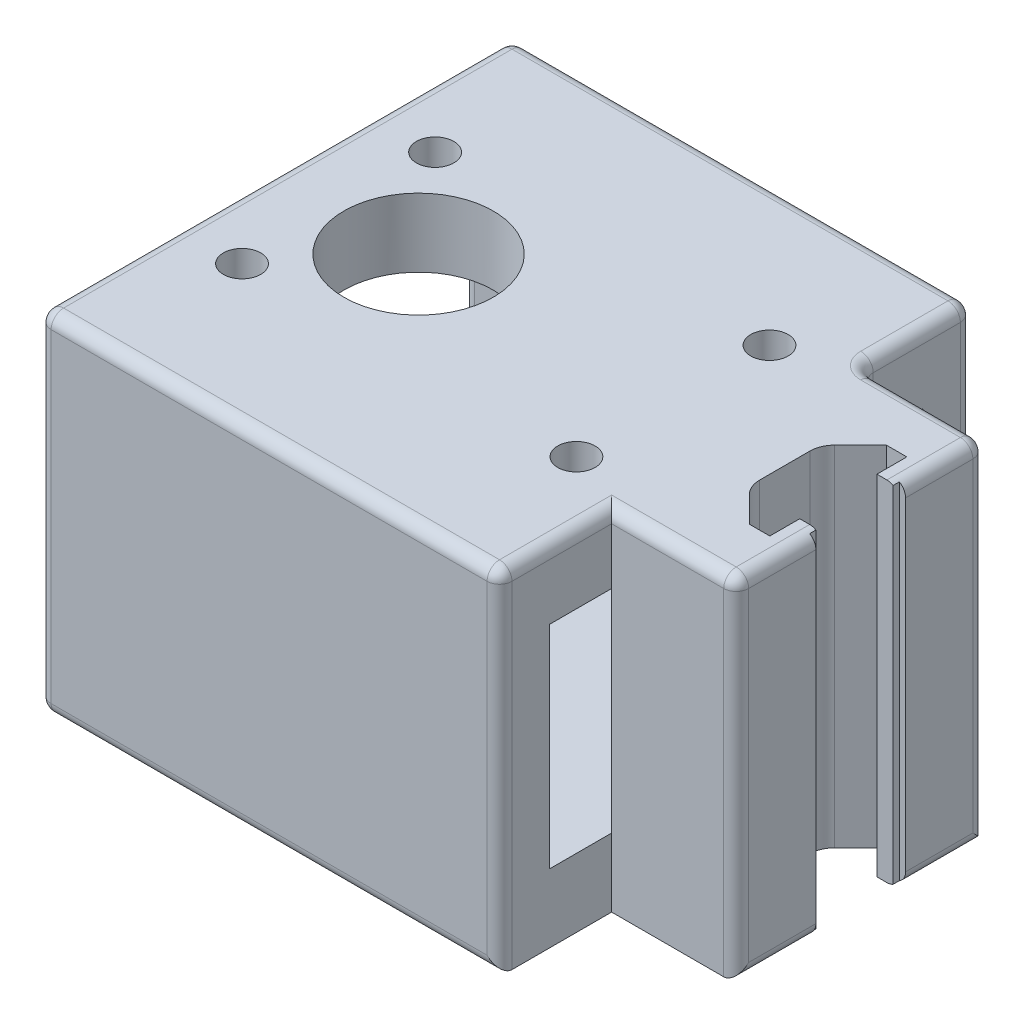
SolidWorks part; units mm, degrees
ref_plane "Front Plane" through (0, 0, 0) normal (0, 0, 1) x (1, 0, 0)
ref_plane "Top Plane" through (0, 0, 0) normal (0, 1, 0) x (1, 0, 0)
ref_plane "Right Plane" through (0, 0, 0) normal (1, 0, 0) x (0, 0, -1)
sketch "Sketch2" plane through (0, 0, 0) normal (1, 0, 0) x (0, 0, -1)
  line L0 (0, -8.5) -> (0, -24.413) construction
  line L1 (19, -14) -> (4, -14)
  line L2 (19, -14) -> (19, 14)
  line L3 (19, 14) -> (-19, 14)
  line L4 (-19, -14) -> (-19, 14)
  line L5 (19, -14) -> (-19, 14) construction
  line L6 (19, 14) -> (-19, -14) construction
  line L7 (-15, -8.5) -> (15, -8.5)
  line L8 (-15, -8.5) -> (-15, 8.5)
  line L9 (-15, 8.5) -> (15, 8.5)
  line L10 (15, -8.5) -> (15, 8.5)
  line L11 (-15, -8.5) -> (15, 8.5) construction
  line L12 (-15, 8.5) -> (15, -8.5) construction
  line L13 (0, -18) -> (-4, -14)
  line L14 (0, -18) -> (4, -14)
  line L15 (-4, -14) -> (-19, -14)
  point P0 (0, 0)
  point P5 (0, 0)
  dimension "D1" = 28
  dimension "D2" = 38
  dimension "D3" = 17
  dimension "D4" = 30
  dimension "D5" = 5.6569
  dimension "D6" = 45
extrude "Boss-Extrude1" add sketch "Sketch2" along normal blind 37
sketch "Sketch3" plane through (0, 14, 0) normal (0, 1, 0) x (1, 0, 0)
  line L0 (37, 19) -> (0, 19) construction
  line L1 (0, 0) -> (37, 0) construction
  line L2 (0, 19) -> (0, -19) construction
  line L3 (37, -19) -> (0, -19) construction
  line L4 (18.5, 19) -> (18.5, -19) construction
  line L5 (37, 19) -> (37, -19) construction
  circle A12 centre (11.5, 0) radius 6
  point P16 (18.5, 0)
  dimension "D1" = 7
  dimension "D5" = 12
extrude "Cut-Extrude1" cut sketch "Sketch3" against normal up to surface (5.5 mm away) contours A12 region at (11.5, 14, 0) up to face at (18.5, 8.5, 0)
sketch "Sketch4" plane through (0, 14, 0) normal (0, 1, 0) x (1, 0, 0)
  line L0 (0, 0) -> (37, 0) construction
  line L1 (37, 19) -> (37, -19) construction
  line L2 (18.5, 0) -> (1.119, 10.0349) construction
  line L3 (18.5, 0) -> (5.0766, 7.75) construction
  circle A0 centre (18.5, 0) radius 15.5 construction
  circle A1 centre (5.0766, 7.75) radius 1.5
  circle A2 centre (18.5, 15.5) radius 1.5 [skipped]
  circle A3 centre (31.9234, 7.75) radius 1.5
  circle A4 centre (31.9234, -7.75) radius 1.5
  circle A5 centre (18.5, -15.5) radius 1.5 [skipped]
  circle A6 centre (5.0766, -7.75) radius 1.5
  dimension "D1" = 31
  dimension "D3" = 3
  dimension "D2" = 30
  dimension "D5" = 15.5
  dimension "D4" = 6
extrude "Cut-Extrude3" cut sketch "Sketch4" against normal up to next
sketch "Sketch6" plane through (0, -14, 0) normal (0, 1, 0) x (1, 0, 0)
  line L0 (37, 0) -> (55.0083, 0) construction
  line L1 (37, 19) -> (37, -19) construction
  line L2 (47, 19.1205) -> (47, -19.1205) construction
  line L3 (47, 3.6) -> (46.5, 3.6)
  line L4 (46.5, 3.6) -> (46.5, 3.1)
  line L5 (46.5, 3.1) -> (45.2, 3.1)
  line L6 (45.2, 3.1) -> (45.2, 5.5)
  line L7 (45.2, 5.5) -> (43.5607, 5.5)
  line L8 (37, 0) -> (50.5625, 13.5625) construction
  line L9 (41.4858, 3.4251) -> (43.5607, 5.5)
  line L10 (40.9, -2.0109) -> (40.9, 2.0109)
  line L11 (41.4858, -3.4251) -> (43.5607, -5.5)
  line L12 (45.2, -5.5) -> (43.5607, -5.5)
  line L13 (45.2, -3.1) -> (45.2, -5.5)
  line L14 (46.5, -3.1) -> (45.2, -3.1)
  line L15 (46.5, -3.6) -> (46.5, -3.1)
  line L16 (47, -3.6) -> (46.5, -3.6)
  line L17 (47, 10) -> (37, 10)
  line L18 (37, 10) -> (37, -10)
  line L19 (37, -10) -> (47, -10)
  line L20 (47, -10) -> (47, -3.6)
  line L21 (47, 10) -> (47, 3.6)
  arc A0 (40.9, 2.0109) -> (41.4858, 3.4251) centre (42.9, 2.0109) cw
  arc A1 (40.9, -2.0109) -> (41.4858, -3.4251) centre (42.9, -2.0109) ccw
  point P27 (40.9, 0)
  line M60 (37, 19) -> (37, 4)
  dimension "D9" = 2
  dimension "D1" = 10
  dimension "D2" = 0.5
  dimension "D3" = 1.8
  dimension "D4" = 7.2
  dimension "D5" = 6.2
  dimension "D6" = 11
  dimension "D7" = 45
  dimension "D8" = 1.5
  dimension "D10" = 3.9
  dimension "D11" = 20
extrude "Boss-Extrude2" add sketch "Sketch6" along normal up to surface (28 mm away) contours L6 L16 L15 L14 L13 | L10 A1 L11 L12 L13 L14 L15 L16 L20 L19 L18 L17 L21 L3 L4 L5 L6 L7 L9 A0 M60 region at (46.75, -14, -3.8236) up to face at (5.0766, 14, 9.25)
fillet "Fillet1" radius 1 28 edges at (42, 14, -10) (0, -8.5, 0) (0, 0, 15) (0, 8.5, 0) (0, 0, -15) (0, -14, 11.5) (0, -16, 2) (0, -16, -2) (0, -14, -11.5) (0, 14, 0) (18.5, -14, -19) (37, 0, -19) (18.5, 14, -19) (0, 0, -19) (18.5, 14, 19) (37, 0, 19) (18.5, -14, 19) (0, 0, 19) (37, 14, -14.5) (37, 11.25, -10) (42, 14, 10) (37, 14, 14.5) (47, 0, -10) (47, 0, 10) (47, -14, 6.8) (47, -14, -6.8) (47, 14, 6.8) (47, 14, -6.8)
